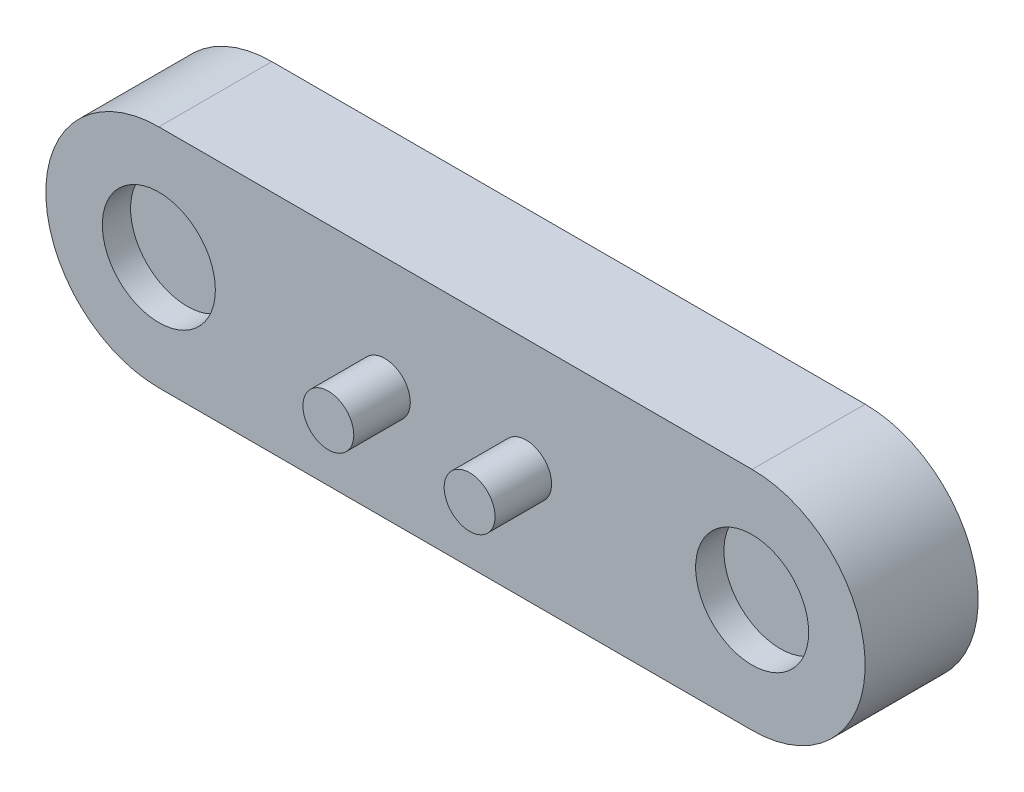
SolidWorks part; units mm, degrees
note: The reader was unsure of these and kept them because the rebuilt part matched: thickness of "Base-Flange1", "Sheet-Metal1", "Sheet-Metal2", "Sheet-Metal3".
ref_plane "Front Plane" through (0, 0, 0) normal (0, 0, 1) x (1, 0, 0)
ref_plane "Top Plane" through (0, 0, 0) normal (0, 1, 0) x (1, 0, 0)
ref_plane "Right Plane" through (0, 0, 0) normal (1, 0, 0) x (0, 0, -1)
sketch "Sketch1" plane through (0, 0, 0) normal (0, 0, 1) x (1, 0, 0)
  line L0 (10.5, 0) -> (0, 0) construction
  line L1 (10.5, -2) -> (0, -2)
  line L2 (10.5, 2) -> (0, 2)
  arc A0 (10.5, -2) -> (10.5, 2) centre (10.5, 0) ccw
  arc A1 (0, 2) -> (0, -2) centre (0, 0) ccw
  point P3 (5.25, 0)
  point P8 (-2, 0)
  point P9 (12.5, 0)
  dimension "D1" = 14.5
  dimension "D2" = 4
base flange "Base-Flange1" sketch "Sketch1" thickness 2 reverse thickness direction no parameters "D1"=10
sketch "Sketch6" plane through (0, 0, 0) normal (0, 0, 1) x (1, 0, 0)
  circle A0 centre (0, 0) radius 1
  circle A1 centre (10.5, 0) radius 1
  dimension "D1" = 2
  dimension "D2" = 2
extrude "Cut-Extrude1" cut sketch "Sketch6" against normal blind 0.5 normal cut yes
sketch "Sketch8" plane through (0, 0, 0) normal (0, 0, 1) x (1, 0, 0)
  circle A0 centre (4, 0) radius 0.45
  circle A1 centre (6.5, 0) radius 0.45
  dimension "D3" = 0.9
  dimension "D4" = 0.9
  dimension "D1" = 4
  dimension "D2" = 2.5
extrude "Boss-Extrude1" add sketch "Sketch8" along normal blind 1
sketch "Bend-Lines1" [suppressed] plane through (0, 0, 0) normal (0, 1, 0) x (1, 0, 0)
sketch "Bounding-Box1" [suppressed] plane through (0, 0, 0) normal (0, 1, 0) x (1, 0, 0)
sheet metal parameters "Sheet-Metal1" thickness 2 parameters "D1"=10
flat pattern "Flat-Pattern1" [suppressed]
sketch "Bend-Lines2" plane through (0, 0, 0) normal (0, 1, 0) x (1, 0, 0)
sketch3d "Bounding-Box2" [suppressed]
  line L0 (-14.9996, -2, 0) -> (1.9996, -2, 0) construction
  line L1 (-14.9996, 2, 0) -> (1.9996, 2, 0) construction
  line L2 (-14.9996, -2, 0) -> (-14.9996, 2, 0) construction
  line L3 (1.9996, -2, 0) -> (1.9996, 2, 0) construction
sheet metal parameters "Sheet-Metal2" thickness 2 parameters "D1"=10
flat pattern "Flat-Pattern1"
sketch "Bend-Lines2" plane through (0, 0, 0) normal (0, 1, 0) x (1, 0, 0)
sketch3d "Bounding-Box2" [suppressed]
  line L0 (-14.9996, -2, 0) -> (1.9996, -2, 0) construction
  line L1 (-14.9996, 2, 0) -> (1.9996, 2, 0) construction
  line L2 (-14.9996, -2, 0) -> (-14.9996, 2, 0) construction
  line L3 (1.9996, -2, 0) -> (1.9996, 2, 0) construction
sheet metal parameters "Sheet-Metal3" thickness 2 parameters "D1"=10
flat pattern "Flat-Pattern1"
sketch "Bend-Lines2" plane through (0, 0, 0) normal (0, 1, 0) x (1, 0, 0)
sketch3d "Bounding-Box2" [suppressed]
  line L0 (-12.4996, -2, 0) -> (1.9996, -2, 0) construction
  line L1 (-12.4996, 2, 0) -> (1.9996, 2, 0) construction
  line L2 (-12.4996, -2, 0) -> (-12.4996, 2, 0) construction
  line L3 (1.9996, -2, 0) -> (1.9996, 2, 0) construction
